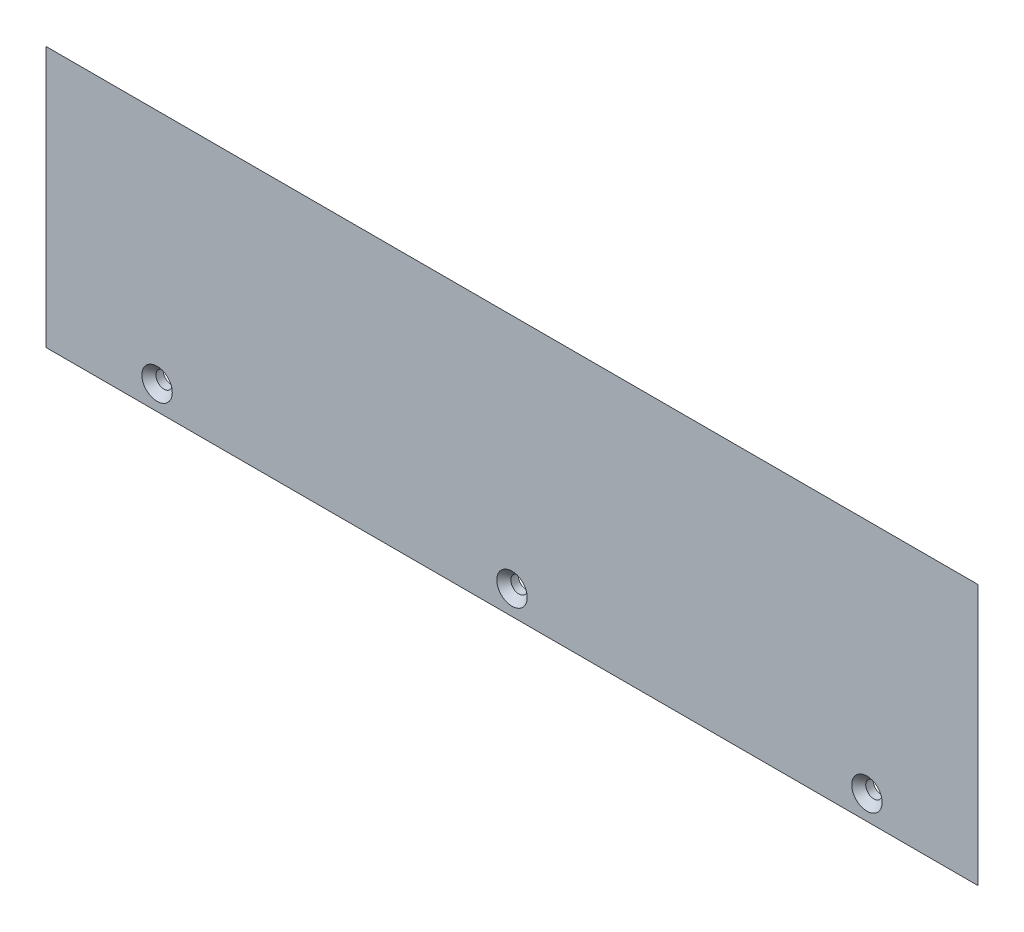
SolidWorks part; units mm, degrees
ref_plane "Front Plane" through (0, 0, 0) normal (0, 0, 1) x (1, 0, 0)
ref_plane "Top Plane" through (0, 0, 0) normal (0, 1, 0) x (1, 0, 0)
ref_plane "Right Plane" through (0, 0, 0) normal (1, 0, 0) x (0, 0, -1)
sketch "Sketch1" plane through (0, 0, 0) normal (0, 0, 1) x (1, 0, 0)
  line L1 (0, 0) -> (193, 0)
  line L2 (0, 0) -> (0, 54)
  line L3 (0, 54) -> (193, 54)
  line L4 (193, 0) -> (193, 54)
  dimension "D1" = 54
  dimension "D2" = 193
extrude "Boss-Extrude1" add sketch "Sketch1" along normal blind 3
chamfer "Chamfer1" distance 3 angle 45 3 edges at (0, 27, 0) (96.5, 54, 0) (193, 27, 0)
sketch "Sketch2" plane through (0, 0, 3) normal (0, 0, 1) x (1, 0, 0)
  line L0 (0, 5) -> (193, 5) construction
  line L1 (0, 54) -> (0, 0) construction
  line L2 (193, 0) -> (193, 54) construction
  line L3 (0, 0) -> (193, 0) construction
  point P8 (23, 5)
  point P9 (96.5, 5)
  point P10 (170, 5)
  dimension "D1" = 5
  dimension "D2" = 23
  dimension "D3" = 23
hole_wizard "CSK for M3 Flat Head Machine Screw1" positions "Sketch4" profile "Sketch3" countersink size "M3" standard "ANSI Metric" end condition through all
sketch "Sketch4" plane through (0, 0, 3) normal (0, 0, 1) x (1, 0, 0)
  point P0 (23, 5)
  point P3 (96.5, 5)
  point P6 (170, 5)
sketch "Sketch3" plane through (23, 5, 3) normal (1, 0, 0) x (0, -1, 0)
  line L0 (0, 0) -> (0, 3)
  line L1 (0, 3) -> (1.7, 3)
  line L2 (1.7, 3) -> (1.7, 1.45)
  line L3 (1.7, 1.45) -> (3.15, 0)
  line L5 (3.15, 0) -> (0, 0)
  line L6 (-1.7, 1.45) -> (-3.15, 0) construction
  line L11 (0, -6.35) -> (0, 107.95) construction
  dimension "Thru Hole Dia." = 3.4
  dimension "Thru Hole Depth" = 3
  dimension "Near C'Sink Dia." = 6.3
  dimension "Near C'Sink Angle" = 90
